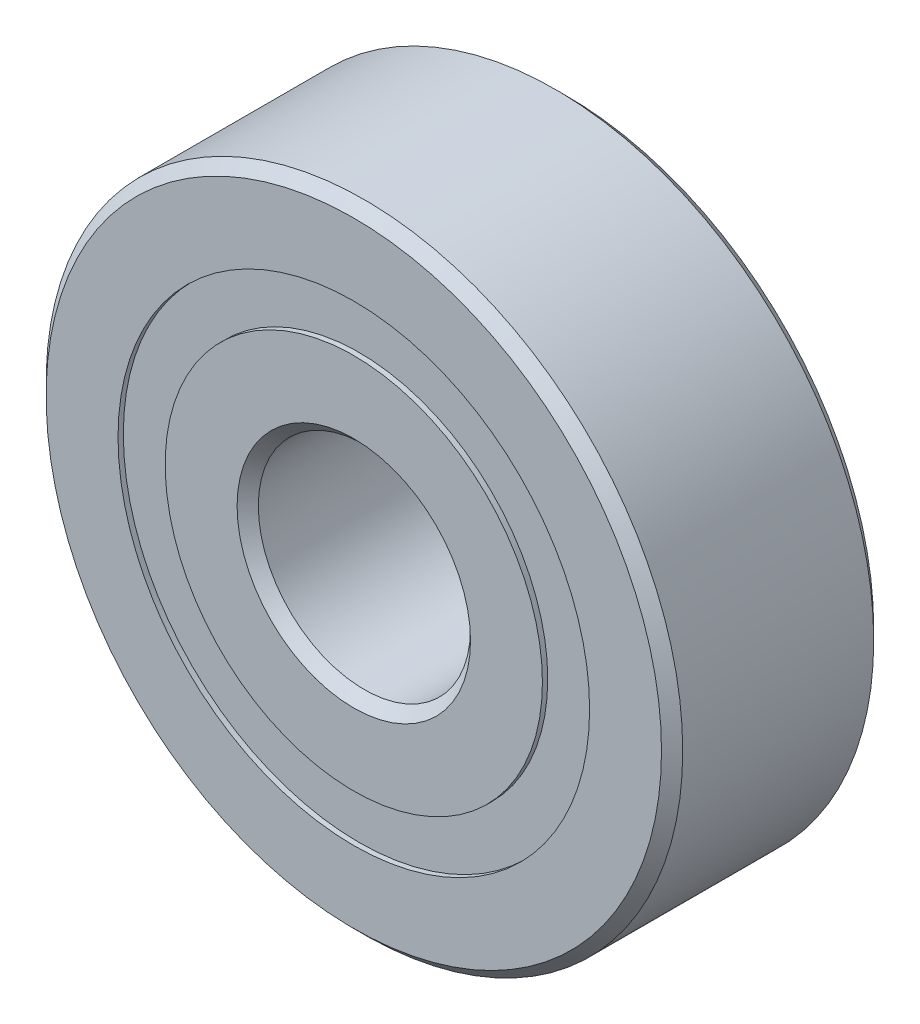
SolidWorks part; units mm, degrees
ref_plane "Front Plane" through (0, 0, 0) normal (0, 0, 1) x (1, 0, 0)
ref_plane "Top Plane" through (0, 0, 0) normal (0, 1, 0) x (1, 0, 0)
ref_plane "Right Plane" through (0, 0, 0) normal (1, 0, 0) x (0, 0, -1)
sketch "Sketch1" plane through (0, 0, 0) normal (1, 0, 0) x (0, 0, -1)
  line L0 (-2, 0) -> (2, 0) construction
  line L1 (0, 6) -> (0, -6) construction
  line L2 (1.8, 6) -> (-1.8, 6)
  line L3 (-1.8, 6) -> (-2, 5.8)
  line L4 (-2, 5.8) -> (-2, 4.4444)
  line L5 (-2, 4.4444) -> (-0.8889, 4.4444)
  line L6 (2, 4.4444) -> (0.8889, 4.4444)
  line L7 (2, 5.8) -> (2, 4.4444)
  line L8 (1.8, 6) -> (2, 5.8)
  line L9 (0, 6) -> (0, 4) construction
  line L10 (0, 4) -> (0, 2) construction
  arc A0 (-0.8889, 4.4444) -> (0.8889, 4.4444) centre (0, 4) cw
  arc A1 (-0.8889, 4.4444) -> (0.8889, 4.4444) centre (0, 4) ccw construction
  point P14 (0, 2)
  point P15 (0, -2)
  dimension "Width" = 4
  dimension "OD" = 12
  dimension "D1" = 45
  dimension "D2" = 0.2
  dimension "D3" = 1.7778
  dimension "Shaft Dia" = 4
  dimension "D4" = 0.4444
revolve "Revolve1" add sketch "Sketch1" angle 360 about L0
sketch "Sketch2" plane through (0, 0, 0) normal (1, 0, 0) x (0, 0, -1)
  line L0 (-2, 3.5556) -> (-0.8889, 3.5556)
  line L1 (-2, 5.8) -> (-2, -5.8) construction
  line L2 (-2, 3.5556) -> (-2, 2.2)
  line L3 (-2, 2.2) -> (-1.8, 2)
  line L4 (-1.8, 2) -> (1.8, 2)
  line L5 (0, 6) -> (0, -6) construction
  line L6 (0, 2) -> (0, 3.0062) construction
  line L7 (0, 3.0062) -> (0, 2) construction
  line L8 (-2, 3.5556) -> (-2, 0.8444) construction
  line L10 (2, 3.5556) -> (0.8889, 3.5556)
  line L11 (2, 3.5556) -> (2, 2.2)
  line L12 (2, 2.2) -> (1.8, 2)
  arc A0 (-0.8889, 3.5556) -> (0.8889, 3.5556) centre (0, 4) ccw
  arc A1 (0.8889, 4.4444) -> (-0.8889, 4.4444) centre (0, 4) ccw construction
  circle A2 centre (0, 4) radius 0.9938 construction
  dimension "D1" = 0.2
  dimension "D2" = 45
revolve "Revolve2" add sketch "Sketch2" angle 360 about L0
sketch "Sketch3" plane through (0, 0, 0) normal (1, 0, 0) x (0, 0, -1)
  line L0 (-0.9938, 4) -> (0.9938, 4)
  line L1 (0, 4) -> (0, 0) construction
  circle A1 centre (0, 4) radius 0.9938 construction
  arc A2 (-0.9938, 4) -> (0.9938, 4) centre (0, 4) cw
  arc A3 (0.8889, 4.4444) -> (-0.8889, 4.4444) centre (0, 4) ccw construction
  dimension "D1" = 1.9876
revolve "Revolve3" add sketch "Sketch3" angle 360 about L0
ref_axis "Axis1" through (0, 0, -2) along (0, 0, 1)
pattern_circular "CirPattern1" count 12 every 30 about axis through (0, 0, -2) along (0, 0, 1) of bodies 104
sketch "Sketch5" plane through (0, 0, 0) normal (1, 0, 0) x (0, 0, -1)
  line L0 (-2, 3.5556) -> (-0.8889, 3.5556) construction
  line L1 (-1.9, 4.4444) -> (-0.9938, 4.4444)
  line L2 (-1.9, 4.4444) -> (-1.9, 3.5556)
  line L3 (-1.9, 3.5556) -> (-0.9938, 3.5556)
  line L4 (-0.9938, 4.4444) -> (-0.9938, 3.5556)
  line L5 (0.9938, 4.4444) -> (1.9, 4.4444)
  line L6 (0.9938, 4.4444) -> (0.9938, 3.5556)
  line L7 (0.9938, 3.5556) -> (1.9, 3.5556)
  line L8 (1.9, 4.4444) -> (1.9, 3.5556)
  line L9 (-2, 4.4444) -> (-0.8889, 4.4444) construction
  line L10 (-1.9, 5.9) -> (-1.9, 4.4444) construction
  line L11 (-1.8, 6) -> (-2, 5.8) construction
  circle A0 centre (0, 4) radius 0.9938 construction
revolve "Revolve5" add sketch "Sketch5" angle 360 about L0
sketch "Sketch6" plane through (0, 0, 0) normal (0, 1, 0) x (1, 0, 0)
  point P0 (6, -2)
  point P1 (6, 2)
ref_axis "Center Axis 1" through (0, 0, -2.8472) along (0, 0, 1)
ref_plane "Contact Plane 1" through (0, 0, 2) normal (0, 0, 1) x (1, 0, 0)
ref_plane "Contact Plane 2" through (0, 0, -2) normal (0, 0, -1) x (-1, 0, 0)
equation "\"D2@Sketch1\" = \"Width@Sketch1\"*.05"
equation "\"D3@Sketch1\" = \"Width@Sketch1\"/2.25"
equation "\"D4@Sketch1\" = \"D3@Sketch1\"/4"
equation "\"Balls@CirPattern1\"=\"D2@Sketch3\"*2*pi/\"D1@Sketch3\"-1"
equation "\"D2@CirPattern1\" = 360/\"Balls@CirPattern1\""
equation "\"D1@Sketch2\"=\"D2@Sketch1\""
equation "\"D1@Sketch6\"=\"Width@Sketch1\""
